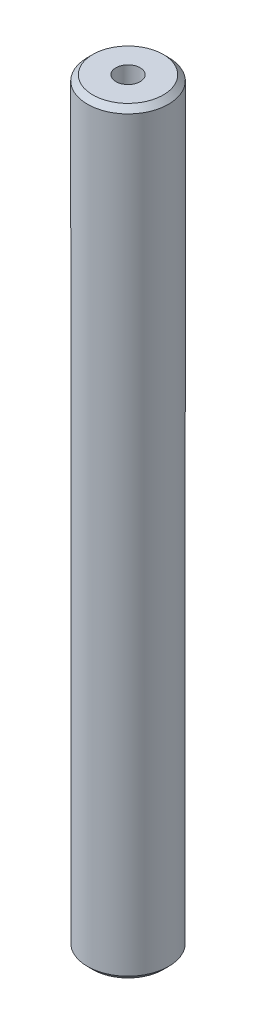
SolidWorks part; units mm, degrees
ref_plane "Front Plane" through (0, 0, 0) normal (0, 0, 1) x (1, 0, 0)
ref_plane "Top Plane" through (0, 0, 0) normal (0, 1, 0) x (1, 0, 0)
ref_plane "Right Plane" through (0, 0, 0) normal (1, 0, 0) x (0, 0, -1)
sketch "Sketch1" plane through (0, 0, 0) normal (0, 1, 0) x (1, 0, 0)
  circle A0 centre (0, 0) radius 22.5
  dimension "SHAFT_OD" = 45
extrude "Boss-Extrude1" add sketch "Sketch1" along normal blind 420.6209
sketch "Sketch2" plane through (0, 0, 0) normal (0, 1, 0) x (1, 0, 0)
  circle A0 centre (0, 0) radius 6.7277
  dimension "BORE_D" = 13.4553
extrude "Cut-Extrude1" cut sketch "Sketch2" along normal through all
chamfer "Chamfer1" distance 2.9685 angle 45 2 edges at (0, 420.6209, 22.5) (0, 0, 22.5)
